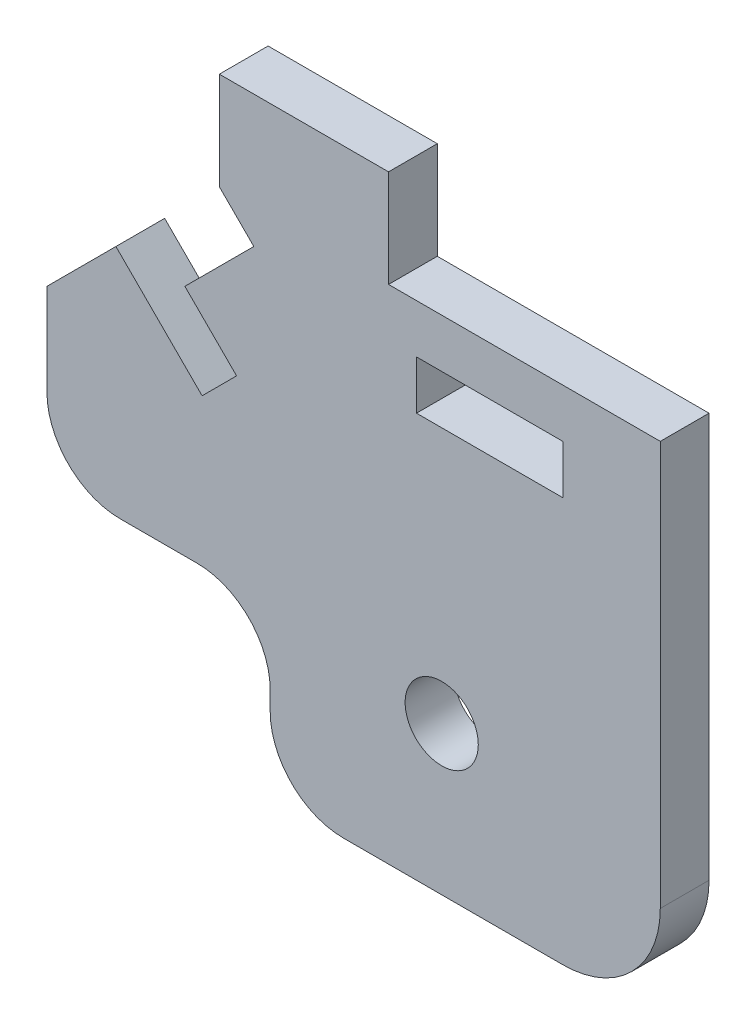
SolidWorks part; units mm, degrees
material "Acrylic (Medium-high impact)"
ref_plane "Front Plane" through (0, 0, 0) normal (0, 0, 1) x (1, 0, 0)
ref_plane "Top Plane" through (0, 0, 0) normal (0, 1, 0) x (1, 0, 0)
ref_plane "Right Plane" through (0, 0, 0) normal (1, 0, 0) x (0, 0, -1)
sketch "Model" plane through (0, 0, 0) normal (0, 0, 1) x (1, 0, 0)
  line L223 (6.364, 1.1716) -> (2.8284, 4.7071)
  line L224 (14.0104, 8.9497) -> (25.1569, 8.9497)
  line L225 (6.1569, -4.8787) -> (5.8284, -4.8787)
  line L226 (21.1569, -11.6414) -> (12.1569, -11.6414)
  line L227 (2.8284, 4.7071) -> (0, 1.8787)
  line L228 (3, -4.8787) -> (5.8284, -4.8787)
  line L229 (7.7782, 2.5858) -> (5.6569, 4.7071)
  line L230 (8.4853, 7.5355) -> (7.0711, 8.9497)
  line L231 (0, -1.8787) -> (0, 1.8787)
  line L232 (9.1569, -8.6414) -> (9.1569, -7.8787)
  line L233 (25.1569, 8.9497) -> (25.1569, -7.6414)
  line L234 (7.0711, 12.9497) -> (14.0104, 12.9497)
  line L235 (21.1569, 4.9497) -> (21.1569, 6.9497)
  line L236 (21.1569, 4.9497) -> (15.1569, 4.9497)
  line L237 (15.1569, 4.9497) -> (15.1569, 6.9497)
  line L238 (15.1569, 6.9497) -> (21.1569, 6.9497)
  line L255 (5.6569, 4.7071) -> (8.4853, 7.5355)
  line L256 (7.0711, 8.9497) -> (7.0711, 12.9497)
  line L257 (6.364, 1.1716) -> (7.7782, 2.5858)
  line L364 (14.0104, 8.9497) -> (14.0104, 12.9497)
  circle A99 centre (16.1917, -5.5589) radius 1.5
  arc A100 (21.1569, -11.6414) -> (25.1569, -7.6414) centre (21.1569, -7.6414) ccw
  arc A101 (9.1569, -8.6414) -> (12.1569, -11.6414) centre (12.1569, -8.6414) ccw
  arc A102 (9.1569, -7.8787) -> (6.1569, -4.8787) centre (6.1569, -7.8787) ccw
  arc A103 (0, -1.8787) -> (3, -4.8787) centre (3, -1.8787) ccw
  dimension "D1" = 3
  dimension "D2" = 4
  dimension "D3" = 3
  dimension "D4" = 5.6569
  dimension "D5" = 5.8284
  dimension "D6" = 6.364
  dimension "D7" = 9.1569
  dimension "D8" = 14.0104
  dimension "D9" = 16.1917
  dimension "D10" = 25.1569
  dimension "D11" = 1.1716
  dimension "D12" = 4.9497
  dimension "D20" = 4.8787
  dimension "D21" = 5.5589
  dimension "D22" = 11.6414
extrude "Boss-Extrude1" add sketch "Model" along normal blind 2
